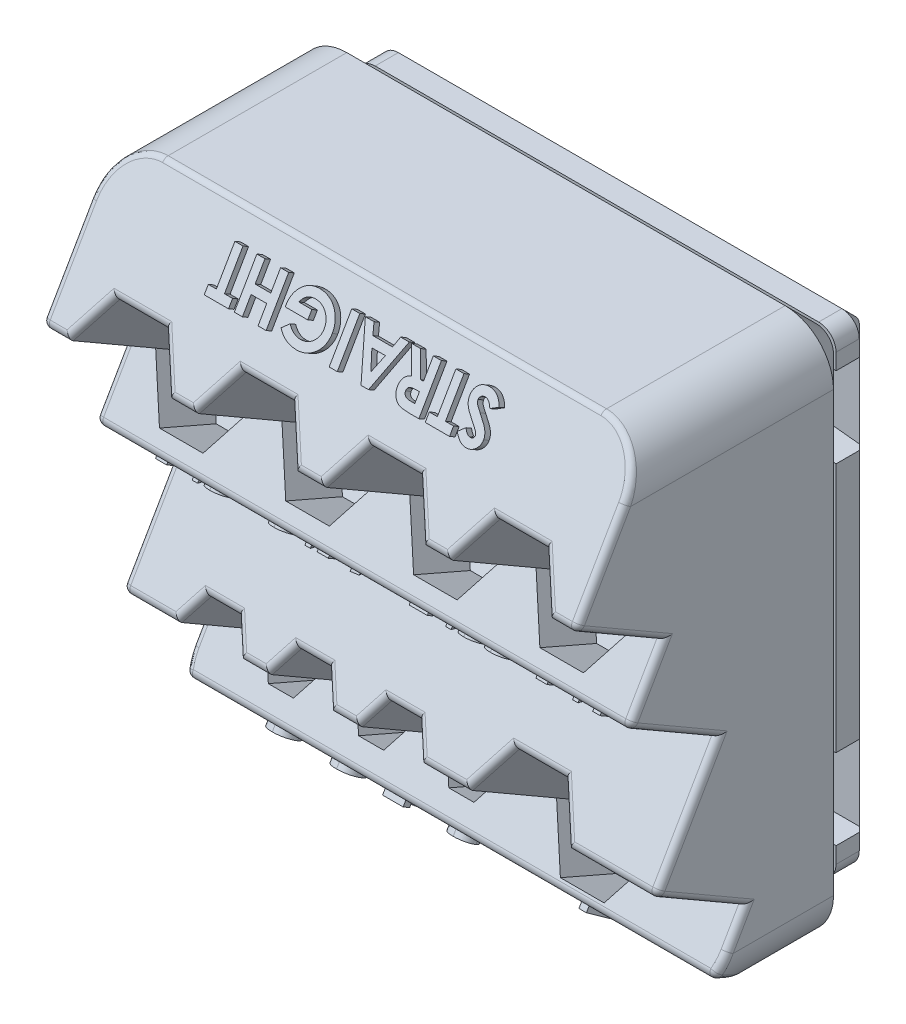
SolidWorks part; units mm, degrees
ref_plane "Front Plane" through (0, 0, 0) normal (0, 0, 1) x (1, 0, 0)
ref_plane "Top Plane" through (0, 0, 0) normal (0, 1, 0) x (1, 0, 0)
ref_plane "Right Plane" through (0, 0, 0) normal (1, 0, 0) x (0, 0, -1)
sketch "Sketch1" plane through (0, 0, 0) normal (0, 0, 1) x (1, 0, 0)
  line L1 (18.55, 18.55) -> (-18.55, 18.55)
  line L2 (18.55, 18.55) -> (18.55, -18.55)
  line L3 (18.55, -18.55) -> (-18.55, -18.55)
  line L4 (-18.55, 18.55) -> (-18.55, -18.55)
  line L5 (18.55, 18.55) -> (-18.55, -18.55) construction
  line L6 (18.55, -18.55) -> (-18.55, 18.55) construction
  point P0 (0, 0)
  dimension "D1" = 37.1
extrude "Boss-Extrude1" add sketch "Sketch1" along normal blind 2.6
sketch "Sketch2" plane through (0, 0, 2.6) normal (0, 0, 1) x (1, 0, 0)
  line L1 (-20.75, 20.75) -> (20.75, 20.75)
  line L2 (-20.75, 20.75) -> (-20.75, -20.75)
  line L3 (-20.75, -20.75) -> (20.75, -20.75)
  line L4 (20.75, 20.75) -> (20.75, -20.75)
  line L5 (-20.75, 20.75) -> (20.75, -20.75) construction
  line L6 (-20.75, -20.75) -> (20.75, 20.75) construction
  point P0 (0, 0)
  dimension "D1" = 41.5
extrude "Boss-Extrude2" add sketch "Sketch2" along normal blind 2.4
sketch "Sketch8" plane through (0, 0, 2.6) normal (0, 0, -1) x (-1, 0, 0)
  line L0 (-18.55, 18.55) -> (-18.55, 5.0094) construction
  line L1 (-18.55, -18.55) -> (-18.55, 18.55) construction
  line L2 (-14.65, 10.1) -> (-18.55, 9.7)
  line L11 (-12.7, 15.95) -> (-18.55, 15.95)
  line L12 (-12.7, 12.7) -> (-12.7, -12.7)
  line L13 (-12.7, -12.7) -> (12.7, -12.7)
  line L14 (12.7, -12.7) -> (12.7, 12.7)
  line L15 (12.7, 12.7) -> (-12.7, 12.7)
  line L16 (-12.7, 9.45) -> (-12.7, -12.7) construction
  line L22 (-18.55, 15.95) -> (-18.55, 9.7)
  arc A0 (-12.7, 15.95) -> (-12.7, 9.45) centre (-12.7, 12.7) cw
  arc A1 (-12.7, 9.45) -> (-14.65, 10.1) centre (-12.7, 12.7) cw
  dimension "D4" = 5.85
  dimension "D5" = 6.25
  dimension "D2" = 6.5
  dimension "D1" = 8.05
extrude "Base Magnet Slot" cut sketch "Sketch8" against normal blind 0.4 and the other way blind 2.2
sketch "Sketch12" plane through (0, 0, 0) normal (0, 0, -1) x (-1, 0, 0)
  line L0 (-12.7, 12.7) -> (-6.2, 12.7) construction
  line L1 (-12.7, 13.7) -> (-6.2, 13.7)
  line L2 (-12.7, 11.7) -> (-6.2, 11.7)
  arc A8 (-14.65, 10.1) -> (-12.7, 15.95) centre (-12.7, 12.7) ccw construction
  arc A9 (-14.65, 10.1) -> (-12.7, 15.95) centre (-12.7, 12.7) ccw construction
  arc A10 (-12.7, 13.7) -> (-12.7, 11.7) centre (-12.7, 12.7) ccw
  arc A11 (-6.2, 11.7) -> (-6.2, 13.7) centre (-6.2, 12.7) ccw
  point P3 (-9.45, 12.7)
  dimension "D1" = 2
  dimension "D2" = 6.5
extrude "Cut-Extrude1" cut sketch "Sketch12" against normal up to surface (2.6 mm away) up to face at (0, 0, 2.6)
mirror "Mirror1" about plane through (0, 0, 0) normal (0, 1, 0) of "Cut-Extrude1", "Base Magnet Slot"
mirror "Mirror2" about plane through (0, 0, 0) normal (1, 0, 0) of "Mirror1"
fillet "Fillet1" radius 1.35 4 edges at (18.55, 18.55, 1.3) (18.55, -18.55, 1.3) (-18.55, -18.55, 1.3) (-18.55, 18.55, 1.3)
fillet "Fillet2" radius 3.75 4 edges at (20.75, -20.75, 3.8) (20.75, 20.75, 3.8) (-20.75, -20.75, 3.8) (-20.75, 20.75, 3.8)
chamfer "Chamfer1" distance 0.8 angle 45 8 edges at (-18.1546, 18.1546, 0) (-18.55, 0, 0) (-18.1546, -18.1546, 0) (0, -18.55, 0) (18.1546, -18.1546, 0) (18.55, 0, 0) (18.1546, 18.1546, 0) (0, 18.55, 0)
chamfer "Chamfer2" distance 2.4 angle 45 8 edges at (20.75, 0, 2.6) (19.6517, 19.6517, 2.6) (19.6517, -19.6517, 2.6) (0, 20.75, 2.6) (0, -20.75, 2.6) (-19.6517, 19.6517, 2.6) (-19.6517, -19.6517, 2.6) (-20.75, 0, 2.6)
other "Move Face1" face at (0, 0, 0) offset 0.25 parameters "D1"=0.25
sketch "Sketch13" plane through (0, 0, 5) normal (0, 0, 1) x (1, 0, 0)
  line L0 (20.75, 17) -> (20.75, -17)
  line L1 (20.75, 17) -> (20.75, -17)
  line L2 (17, -20.75) -> (-17, -20.75)
  line L3 (17, -20.75) -> (-17, -20.75)
  line L4 (-20.75, -17) -> (-20.75, 17)
  line L5 (-20.75, -17) -> (-20.75, 17)
  line L6 (-17, 20.75) -> (17, 20.75)
  line L7 (-17, 20.75) -> (17, 20.75)
  arc A0 (17, -20.75) -> (20.75, -17) centre (17, -17) ccw
  arc A1 (17, -20.75) -> (20.75, -17) centre (17, -17) ccw
  arc A2 (-20.75, -17) -> (-17, -20.75) centre (-17, -17) ccw
  arc A3 (-20.75, -17) -> (-17, -20.75) centre (-17, -17) ccw
  arc A4 (-17, 20.75) -> (-20.75, 17) centre (-17, 17) ccw
  arc A5 (-17, 20.75) -> (-20.75, 17) centre (-17, 17) ccw
  arc A6 (20.75, 17) -> (17, 20.75) centre (17, 17) ccw
  arc A7 (20.75, 17) -> (17, 20.75) centre (17, 17) ccw
extrude "Boss-Extrude3" add sketch "Sketch13" along normal blind 20
sketch "Sketch14" plane through (-20.75, 0, 0) normal (-1, 0, 0) x (0, 0, 1)
  line L0 (5, -20.75) -> (5, -12.5228) construction
  line L1 (18.7583, -10.3529) -> (13.9333, -1.9957)
  line L2 (9.75, -20.75) -> (-0.1084, -3.6747) construction
  line L3 (9.75, -20.75) -> (14.0801, -18.25)
  line L4 (14.0801, -18.25) -> (11.8301, -14.3529)
  line L5 (11.8301, -14.3529) -> (18.7583, -10.3529)
  line L6 (25, -20.75) -> (5, -20.75) construction
  line L8 (9.75, -20.75) -> (9.75, 20.75) construction
  line L16 (5, -20.75) -> (5, 20.75) construction
  line L17 (13.9333, -1.9957) -> (25, 4.3936)
  line L22 (25, -20.75) -> (9.75, -20.75)
  line L24 (25, 17) -> (25, -17) construction
  line L25 (25, 4.3936) -> (25, -20.75)
  dimension "D1" = 9.65
  dimension "D2" = 5
  dimension "D3" = 4.5
  dimension "D4" = 8
  dimension "D5" = 30
  dimension "D8" = 4.75
extrude "Cut-Extrude2" cut sketch "Sketch14" against normal through all
sketch "Sketch15" plane through (0, 5.5344, 9.5858) normal (0, 0.5, 0.866) x (1, 0, 0)
  line L0 (-20.75, -18.345) -> (20.75, -18.345) construction
  line L2 (2.4537, -18.345) -> (1.2269, -16.22)
  line L3 (1.2269, -16.22) -> (-1.2269, -16.22)
  line L4 (-1.2269, -16.22) -> (-2.4537, -18.345)
  line L5 (-2.4537, -18.345) -> (-1.2269, -20.47)
  line L6 (-1.2269, -20.47) -> (1.2269, -20.47)
  line L7 (1.2269, -20.47) -> (2.4537, -18.345)
  line L20 (8.0514, -21.72) -> (11.9486, -21.72)
  line L21 (-4.5463, -18.345) -> (-5.7731, -16.22)
  line L22 (-5.7731, -16.22) -> (-8.2269, -16.22)
  line L23 (-8.2269, -16.22) -> (-9.4537, -18.345)
  line L24 (-9.4537, -18.345) -> (-8.2269, -20.47)
  line L25 (-8.2269, -20.47) -> (-5.7731, -20.47)
  line L26 (-5.7731, -20.47) -> (-4.5463, -18.345)
  line L27 (-27.75, -18.345) -> (13.75, -18.345) construction
  line L34 (-11.5463, -18.345) -> (-12.7731, -16.22)
  line L35 (11.9486, -21.72) -> (13.8971, -18.345)
  line L36 (13.8971, -18.345) -> (11.9486, -14.97)
  line L37 (11.9486, -14.97) -> (8.0514, -14.97)
  line L38 (8.0514, -14.97) -> (6.1029, -18.345)
  line L39 (6.1029, -18.345) -> (8.0514, -21.72)
  line L47 (-12.7731, -16.22) -> (-15.2269, -16.22)
  line L48 (-15.2269, -16.22) -> (-16.4537, -18.345)
  line L49 (-16.4537, -18.345) -> (-15.2269, -20.47)
  line L50 (-15.2269, -20.47) -> (-12.7731, -20.47)
  line L51 (-12.7731, -20.47) -> (-11.5463, -18.345)
  line L53 (-34.75, -18.345) -> (6.75, -18.345) construction
  circle A0 centre (0, -18.345) radius 2.125 construction
  circle A1 centre (-14, -18.345) radius 2.125 construction
  circle A2 centre (10, -18.345) radius 3.375 construction
  circle A3 centre (-7, -18.345) radius 2.125 construction
  dimension "D1" = 4.25
  dimension "D4" = 14
  dimension "D5" = 10
  dimension "D2" = 6.75
  dimension "D3" = 3
extrude "Front-Hex-Holes" cut sketch "Sketch15" against normal blind 13
sketch "Sketch16" plane through (0, -19.7844, 11.4225) normal (0, -0.866, 0.5) x (1, 0, 0)
  line L1 (-7, 11.0687) -> (-7, -11.4139) construction
  line L2 (-17, -1.9313) -> (17, -1.9313)
  line L3 (20.5355, 3.0687) -> (-20.5355, 3.0687)
  line L4 (-17, -1.9313) -> (17, -1.9313) construction
  line L6 (-5.7731, 11.0687) -> (-8.2269, 11.0687) construction
  line L7 (13.625, -4.9313) -> (0.375, -2.9313) construction
  line L10 (0, 11.0687) -> (0, -11.4139) construction
  line L11 (-13.625, -2.9313) -> (-0.375, -2.9313)
  line L12 (-13.625, -2.9313) -> (-13.625, -4.9313)
  line L13 (-13.625, -4.9313) -> (-0.375, -4.9313)
  line L14 (-0.375, -2.9313) -> (-0.375, -4.9313)
  line L15 (-13.625, -2.9313) -> (-0.375, -4.9313) construction
  line L16 (-13.625, -4.9313) -> (-0.375, -2.9313) construction
  line L17 (1.2269, 11.0687) -> (-1.2269, 11.0687) construction
  line L18 (13.625, -2.9313) -> (0.375, -4.9313) construction
  line L20 (0.375, -2.9313) -> (0.375, -4.9313)
  line L21 (13.625, -4.9313) -> (0.375, -4.9313)
  line L22 (13.625, -2.9313) -> (13.625, -4.9313)
  line L23 (13.625, -2.9313) -> (0.375, -2.9313)
  ellipse E2 centre (17, 5.5687) end of major axis (17, 13.0687) minor radius 3.75 (17, -1.9313) -> (20.5355, 3.0687) ccw
  ellipse E3 centre (-17, 5.5687) end of major axis (-17, 13.0687) minor radius 3.75 (-20.5355, 3.0687) -> (-17, -1.9313) ccw
  point P32 (-7, -3.9313)
  point P42 (7, -3.9313)
  dimension "D2" = 1
  dimension "D3" = 2
  dimension "D4" = 13.25
  dimension "D1" = 0
extrude "Front-Magnet-Holes" cut sketch "Sketch16" against normal offset from surface (7.625 mm away) 1 up to face at (-14, -11.7626, 12.0667) offset beyond the face yes
sketch "Sketch17" plane through (0, -7.5301, 4.3475) normal (0, -0.866, 0.5) x (1, 0, 0)
  line L0 (0, 11.0687) -> (0, 23.8474) construction
  line L1 (-16.625, 13.0687) -> (-3.375, 13.0687)
  line L2 (-16.625, 13.0687) -> (-16.625, 11.0687)
  line L3 (-16.625, 11.0687) -> (-3.375, 11.0687)
  line L4 (-3.375, 13.0687) -> (-3.375, 11.0687)
  line L5 (-16.625, 13.0687) -> (-3.375, 11.0687) construction
  line L6 (-16.625, 11.0687) -> (-3.375, 13.0687) construction
  line L7 (1.2269, 11.0687) -> (-1.2269, 11.0687) construction
  line L8 (20.75, 23.8474) -> (-20.75, 23.8474) construction
  line L10 (-20.75, 11.0687) -> (20.75, 11.0687) construction
  line L11 (16.625, 11.0687) -> (3.375, 13.0687) construction
  line L12 (16.625, 13.0687) -> (3.375, 11.0687) construction
  line L13 (3.375, 13.0687) -> (3.375, 11.0687)
  line L14 (16.625, 11.0687) -> (3.375, 11.0687)
  line L15 (16.625, 13.0687) -> (16.625, 11.0687)
  line L16 (16.625, 13.0687) -> (3.375, 13.0687)
  point P0 (-10, 12.0687)
  point P19 (10, 12.0687)
  dimension "D1" = 2
  dimension "D2" = 13.25
  dimension "D3" = 10
sketch "Sketch18" plane through (0, -7.5301, 4.3475) normal (0, -0.866, 0.5) x (1, 0, 0)
  line L0 (-20.75, 11.0687) -> (20.75, 11.0687) construction
  line L2 (-20.75, 19.0687) -> (20.75, 19.0687)
  line L3 (-20.75, 19.0687) -> (-20.75, 27.0687)
  line L4 (-20.75, 27.0687) -> (20.75, 27.0687)
  line L5 (20.75, 19.0687) -> (20.75, 27.0687)
  line L7 (-20.75, 23.8474) -> (-20.75, 11.0687) construction
  line L8 (20.75, 23.8474) -> (20.75, 11.0687) construction
  dimension "D1" = 8
  dimension "D2" = 41.5
  dimension "D3" = 8
extrude "Cut-Extrude5" cut sketch "Sketch18" against normal blind 5.375
sketch "Sketch20" plane through (0, -2.8752, 1.66) normal (0, -0.866, 0.5) x (1, 0, 0)
  line L1 (-20.75, 26.9507) -> (20.75, 26.9507)
  line L2 (-20.75, 26.9507) -> (-20.75, 34.9507)
  line L3 (-20.75, 34.9507) -> (20.75, 34.9507)
  line L4 (20.75, 26.9507) -> (20.75, 34.9507)
  dimension "D1" = 8
  dimension "D2" = 41.5
extrude "Cut-Extrude6" cut sketch "Sketch20" against normal through all
sketch "Sketch21" plane through (0, 13.4753, 23.34) normal (0, 0.5, 0.866) x (1, 0, 0)
  line L0 (0, 8.4) -> (0, -22.845) construction
  line L1 (-17, 8.4) -> (17, 8.4) construction
  line L2 (20.5355, -22.845) -> (-20.5355, -22.845) construction
  line L3 (20.75, -3.32) -> (-20.75, -3.32) construction
  line L18 (20.75, -3.32) -> (-20.75, -3.32) construction
  line L19 (-6.9072, -6.695) -> (-3.0101, -6.695)
  line L26 (-16.7014, -6.695) -> (-12.8043, -6.695)
  line L27 (-12.8043, -6.695) -> (-10.8558, -3.32)
  line L29 (-10.8558, -3.32) -> (-12.8043, 0.055)
  line L30 (-12.8043, 0.055) -> (-16.7014, 0.055)
  line L31 (-16.7014, 0.055) -> (-18.65, -3.32)
  line L32 (-18.65, -3.32) -> (-16.7014, -6.695)
  line L37 (-3.0101, -6.695) -> (-1.0615, -3.32)
  line L38 (-1.0615, -3.32) -> (-3.0101, 0.055)
  line L39 (-3.0101, 0.055) -> (-6.9072, 0.055)
  line L40 (-6.9072, 0.055) -> (-8.8558, -3.32)
  line L41 (-8.8558, -3.32) -> (-6.9072, -6.695)
  line L42 (30.5442, -3.32) -> (-10.9558, -3.32) construction
  line L43 (-30.5442, -3.32) -> (10.9558, -3.32) construction
  line L44 (8.8558, -3.32) -> (6.9072, -6.695)
  line L45 (6.9072, 0.055) -> (8.8558, -3.32)
  line L46 (3.0101, 0.055) -> (6.9072, 0.055)
  line L47 (1.0615, -3.32) -> (3.0101, 0.055)
  line L48 (3.0101, -6.695) -> (1.0615, -3.32)
  line L49 (18.65, -3.32) -> (16.7014, -6.695)
  line L50 (16.7014, 0.055) -> (18.65, -3.32)
  line L51 (12.8043, 0.055) -> (16.7014, 0.055)
  line L52 (10.8558, -3.32) -> (12.8043, 0.055)
  line L53 (12.8043, -6.695) -> (10.8558, -3.32)
  line L54 (16.7014, -6.695) -> (12.8043, -6.695)
  line L55 (6.9072, -6.695) -> (3.0101, -6.695)
  circle A0 centre (-14.7529, -3.32) radius 3.375 construction
  circle A1 centre (-4.9587, -3.32) radius 3.375 construction
  circle A2 centre (4.9587, -3.32) radius 3.375 construction
  circle A3 centre (14.7529, -3.32) radius 3.375 construction
  dimension "D1" = 6.75
  dimension "D2" = 2.1
  dimension "D3" = 2
extrude "Rear-Hex-Holes" cut sketch "Sketch21" against normal blind 13
extrude "Rear-Magnet-Holes" cut sketch "Sketch17" against normal offset from surface (9.75 mm away) 1 up to face at (-14.7529, 10.273, 17.6833) offset beyond the face yes
draft "Rear-Hex-Draft" type of draft neutral plane draft angle 5 faces to draft 4 face at (-14.7529, 2.4568, 17.6454) face at (-4.9587, 2.4568, 17.6454) face at (4.9587, 2.4568, 17.6454) face at (14.7529, 2.4568, 17.6454) neutral plane through (0, 6.9753, 12.0817) neutral plane normal (0, 0.5, 0.866) parameters "D1"=5
draft "Front-Hex-Draft" type of draft neutral plane draft angle 5 faces to draft 4 face at (10, -18.5257, 11.3526) face at (-14, -17.4432, 10.7276) face at (-7, -17.4432, 10.7276) face at (0, -17.4432, 10.7276) neutral plane through (0, -0.9656, -1.6725) neutral plane normal (0, 0.5, 0.866) parameters "D1"=5
sketch "Sketch22" plane through (0, -19.7844, 11.4225) normal (0, -0.866, 0.5) x (1, 0, 0)
  line L0 (-14, 11.0687) -> (-14, -1.9313) construction
  line L2 (17, -1.9313) -> (-17, -1.9313) construction
  line L3 (-7, 11.0687) -> (-7, -1.9313) construction
  line L4 (-5.7731, 11.0687) -> (-8.2269, 11.0687) construction
  line L5 (0, 11.0687) -> (0, -1.9313) construction
  line L6 (1.2269, 11.0687) -> (-1.2269, 11.0687) construction
  line L7 (-12.7731, 11.0687) -> (-15.2269, 11.0687) construction
  line L9 (10, 11.0687) -> (10, -1.9313) construction
  line L11 (-17.4207, -1.1813) -> (-10.5793, -1.1813) construction
  line L12 (-10.4207, -1.1813) -> (-3.5793, -1.1813) construction
  line L13 (-3.4207, -1.1813) -> (3.4207, -1.1813) construction
  line L14 (-16.7759, -1.1813) -> (-9.9345, -1.1813) construction
  line L15 (6.0347, -1.1813) -> (13.9653, -1.1813) construction
  line L16 (-12.7731, 11.0687) -> (-15.2269, 11.0687) construction
  line L17 (11.9486, 11.0687) -> (8.0514, 11.0687) construction
  line L18 (11.9486, 11.0687) -> (8.0514, 11.0687) construction
  text T0 "2" font "Century Gothic" height 3.5
  text T1 "2.5\r\n" font "Century Gothic" height 3.5
  text T2 "3" font "Century Gothic" height 3.5
  text T4 "A" font "Century Gothic" height 3.5
  point P2 (0, 0)
  point P15 (-14, 11.0687)
  point P21 (10, 11.0687)
  point P22 (6.0347, -1.1813)
  point P34 (-14, -1.1813)
  point P35 (-7, -1.1813)
  point P36 (0, -1.1813)
  point P38 (10, -1.1813)
  dimension "D1" = 0.75
sketch "Sketch23" plane through (0, -7.5301, 4.3475) normal (0, -0.866, 0.5) x (1, 0, 0)
  line L0 (-14.7529, 26.9507) -> (-14.7529, 13.0687) construction
  line L1 (-10.0981, 14.3187) -> (0.1808, 14.3187) construction
  line L2 (-3.375, 13.0687) -> (-16.625, 13.0687) construction
  line L3 (-4.9587, 26.9507) -> (-4.9587, 13.0687) construction
  line L4 (10.0981, 14.3187) -> (-0.1808, 14.3187) construction
  line L5 (14.7529, 26.9507) -> (14.7529, 13.0687) construction
  line L7 (16.625, 13.0687) -> (3.375, 13.0687) construction
  line L8 (-19.8923, 14.3187) -> (-9.6135, 14.3187) construction
  line L9 (4.9587, 26.9507) -> (4.9587, 13.0687) construction
  line L10 (9.6135, 14.3187) -> (19.8923, 14.3187) construction
  line L11 (16.7014, 26.9507) -> (12.8043, 26.9507) construction
  line L12 (6.9072, 26.9507) -> (3.0101, 26.9507) construction
  line L13 (-3.0101, 26.9507) -> (-6.9072, 26.9507) construction
  line L14 (-12.8043, 26.9507) -> (-16.7014, 26.9507) construction
  line L15 (16.7014, 26.9507) -> (12.8043, 26.9507) construction
  line L16 (6.9072, 26.9507) -> (3.0101, 26.9507) construction
  line L17 (-3.0101, 26.9507) -> (-6.9072, 26.9507) construction
  line L18 (-12.8043, 26.9507) -> (-16.7014, 26.9507) construction
  line L19 (16.625, 13.0687) -> (3.375, 13.0687) construction
  text T0 "1/8" font "Century Gothic" height 3.1
  text T1 "3/16" font "Century Gothic" height 3.1
  text T2 "1/4" font "Century Gothic" height 3.1
  text T3 "5/32" font "Century Gothic" height 3.1
  point P23 (-14.7529, 14.3187)
  point P25 (14.7529, 14.3187)
  point P26 (0, 0)
  point P30 (-14.7529, 26.9507)
  point P33 (14.7529, 26.9507)
  point P36 (4.9587, 14.3187)
  point P37 (-4.9587, 14.3187)
  point P38 (-18.6242, 14.0687)
  point P39 (-19.8923, 14.0687)
  dimension "D1" = 1.25
extrude "Rear Text" add sketch "Sketch23" along normal blind 0.5
extrude "Front-Text" add sketch "Sketch22" along normal blind 0.5
fillet "Fillet34" radius 0.5 58 edges at (19.1651, -20.0619, 10.9419) (0, -20.75, 9.75) (20.696, -17.6341, 13.7246) (-20.696, -17.6341, 13.7246) (-20.75, 13.8001, 23.1525) (-19.6517, 19.6517, 19.7741) (0, 20.75, 19.14) (19.6517, 19.6517, 19.7741) (20.75, 13.8001, 23.1525) (19.7, 10.6001, 25) (-17.6757, 12.0615, 24.1563) (-19.7, 10.6001, 25) (-19.1651, -20.0619, 10.9419) (0, -18.25, 14.0801) (20.75, -15.6764, 12.5943) (-20.75, -15.6764, 12.5943) (20.75, -12.3529, 15.2942) (17.3236, -10.3529, 18.7583) (20.75, -6.1743, 16.3458) (-18.6019, -10.3529, 18.7583) (-20.75, -12.3529, 15.2942) (-20.75, -6.1743, 16.3458) (-20.75, 0.0043, 17.3974) (20.75, 0.0043, 17.3974) (0, 2.0043, 20.8615) (20.75, 4.3317, 19.5178) (-20.75, 4.3317, 19.5178) (20.75, 8.6296, 21.587) (-20.75, 8.6296, 21.587) (4.2783, -10.3529, 18.7583) (-3.5, -10.3529, 18.7583) (-10.5, -10.3529, 18.7583) (12.9228, -8.8915, 17.9146) (10, -7.43, 17.0708) (7.0772, -8.8915, 17.9146) (1.8403, -9.4327, 18.2271) (0, -8.5126, 17.6958) (-1.8403, -9.4327, 18.2271) (-5.1597, -9.4327, 18.2271) (-7, -8.5126, 17.6958) (-8.8403, -9.4327, 18.2271) (-12.1597, -9.4327, 18.2271) (-15.8403, -9.4327, 18.2271) (-14, -8.5126, 17.6958) (17.6757, 12.0615, 24.1563) (14.7529, 13.523, 23.3125) (11.83, 12.0615, 24.1563) (9.8558, 10.6001, 25) (7.8815, 12.0615, 24.1563) (4.9587, 13.523, 23.3125) (2.0358, 12.0615, 24.1563) (0, 10.6001, 25) (-2.0358, 12.0615, 24.1563) (-4.9587, 13.523, 23.3125) (-7.8815, 12.0615, 24.1563) (-9.8558, 10.6001, 25) (-11.83, 12.0615, 24.1563) (-14.7529, 13.523, 23.3125)
sketch "Sketch24" plane through (0, 13.4753, 23.34) normal (0, 0.5, 0.866) x (1, 0, 0)
  line L0 (0, 8.1114) -> (0, -6.0135) construction
  line L1 (17, 8.1114) -> (-17, 8.1114) construction
  line L2 (-16.5175, 6.4265) -> (16.5175, 6.4265) construction
  text T0 "STRAIGHT" font "Century Gothic" height 3.5
  point P8 (0, 6.4265)
extrude "Boss-Extrude4" add sketch "Sketch24" along normal blind 0.5
equation "\"MagnetHoleDia\"= 6.5"
equation "\"MagnetPressGap\"= 5.85"
equation "\"MagnetSlotDepth\"= 2.6"
